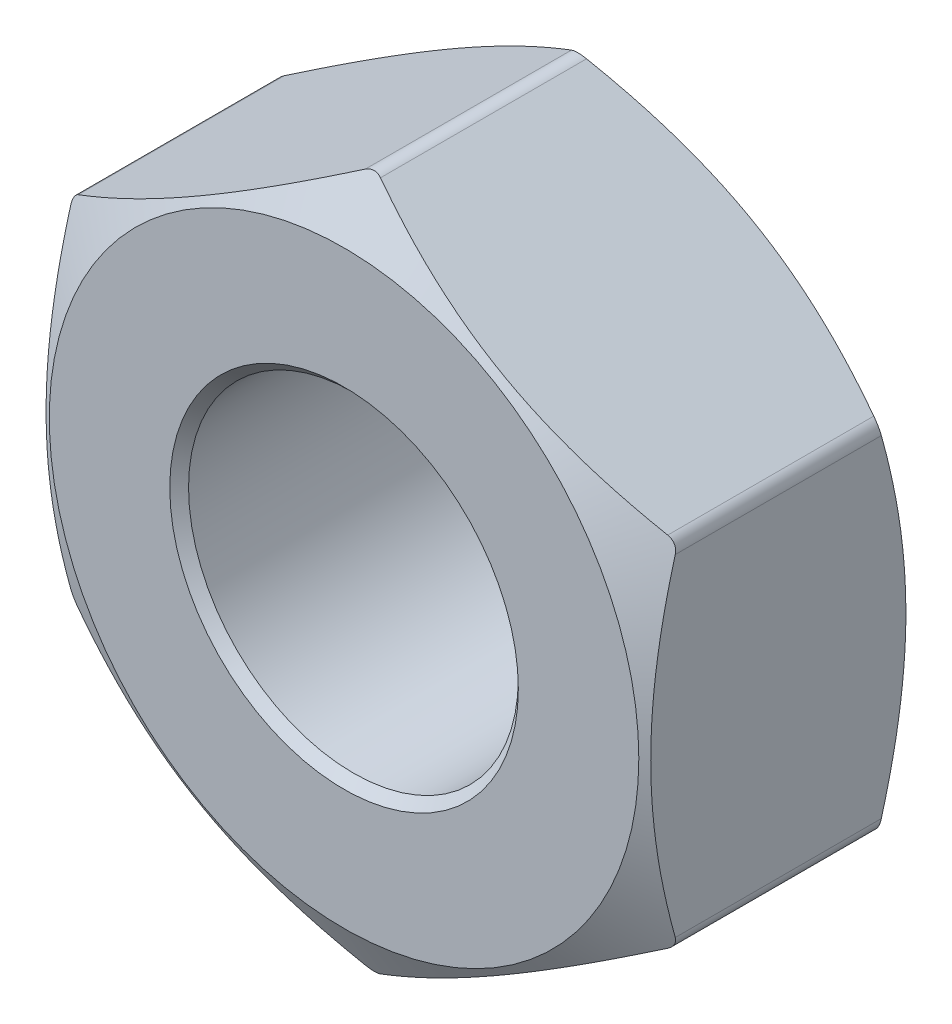
SolidWorks part; units mm, degrees
ref_plane "Front Plane" through (0, 0, 0) normal (0, 0, 1) x (1, 0, 0)
ref_plane "Top Plane" through (0, 0, 0) normal (0, 1, 0) x (1, 0, 0)
ref_plane "Right Plane" through (0, 0, 0) normal (1, 0, 0) x (0, 0, -1)
sketch "Sketch1" plane through (0, 0, 0) normal (1, 0, 0) x (0, 0, -1)
  line L0 (-1.2, 0) -> (1.2, 0) construction
  line L1 (-1.2, -2.75) -> (-1.2, 2.75) construction
  line L2 (1.2, -2.75) -> (1.2, 2.75) construction
  line L3 (-1.2, -1.5) -> (-1.2, 1.5) construction
  line L4 (-1.6688, 1.5541) -> (-1.4188, 1.1211) construction
  line L5 (-1.4188, 1.1211) -> (-1.1688, 1.5541) construction
  line L6 (-1.1688, 1.5541) -> (-1.6688, 1.5541) construction
  line L7 (-1.6531, 1.5271) -> (-1.1844, 1.5271) construction
  line L8 (-1.6375, 1.5) -> (-1.2, 1.5) construction
  line L9 (-1.45, 1.1752) -> (-1.3875, 1.1752) construction
  line L10 (-1.4188, 1.1752) -> (-1.4188, 1.1211) construction
  line L11 (-1.4188, 1.5541) -> (-1.4188, 1.5) construction
  line L12 (-1.2, 1.5854) -> (-1.1146, 1.5) construction
  point P4 (0, 0)
  point P7 (-1.2, 0)
  point P11 (1.2, 0)
  point P14 (-1.2, 0)
  point P26 (-1.4188, 1.5271)
  point P27 (-1.2, -1.5)
  dimension "Height" = 2.4
  dimension "Width" = 5.5
  dimension "Thread Size" = 3
  dimension "D1" = 60
  dimension "Thread Pitch" = 0.5
  dimension "D2" = 0.0625
  dimension "D3" = 45
sketch "Sketch2" plane through (0, 0, 0) normal (0, 0, 1) x (1, 0, 0)
  line L1 (0, 3.1754) -> (-2.75, 1.5877)
  line L2 (-2.75, 1.5877) -> (-2.75, -1.5877)
  line L3 (-2.75, -1.5877) -> (0, -3.1754)
  line L4 (0, -3.1754) -> (2.75, -1.5877)
  line L5 (2.75, -1.5877) -> (2.75, 1.5877)
  line L6 (2.75, 1.5877) -> (0, 3.1754)
  circle A0 centre (0, 0) radius 2.75 construction
  circle A1 centre (0, 0) radius 1.5
extrude "Boss-Extrude1" add sketch "Sketch2" along normal up to vertex (1.2 mm away) and the other way up to vertex (1.2 mm away) up to point (0, -2.75, 1.2) other way up to point (0, -2.75, -1.2)
sketch "Sketch3" plane through (0, 0, 1.2) normal (0, 0, 1) x (1, 0, 0)
  circle A0 centre (0, 0) radius 2.6812
  dimension "D1" = 5.3625
extrude "Cut-Extrude1" cut sketch "Sketch3" against normal through all draft 60 flip side to cut
fillet "Fillet1" radius 0.1375 6 edges at (2.75, -1.5877, -0.1427) (0, -3.1754, -0.1427) (-2.75, -1.5877, -0.1427) (-2.75, 1.5877, -0.1427) (2.75, 1.5877, -0.1427) (0, 3.1754, -0.1427)
sketch "Sketch8" plane through (0, 0, 1.2) normal (0, 0, 1) x (1, 0, 0)
  circle A0 centre (0, 0) radius 1.5854
extrude "Cut-Extrude4" cut sketch "Sketch8" against normal through all draft 45
mirror "Mirror1" about plane through (0, 0, 0) normal (0, 0, 1) of "Cut-Extrude4", "Cut-Extrude1"
sketch "Sketch4" [suppressed] plane through (0, 0, 0) normal (1, 0, 0) x (0, 0, -1)
  line L1 (-1.6531, 1.5271) -> (-1.45, 1.1752)
  line L2 (-1.45, 1.1752) -> (-1.3875, 1.1752)
  line L3 (-1.3875, 1.1752) -> (-1.1844, 1.5271)
  line L4 (-1.6531, 1.5271) -> (-1.1844, 1.5271) construction
  line L5 (-1.6531, 1.5271) -> (-1.1844, 1.5271)
sketch "Sketch5" [suppressed] plane through (0, 0, 1.2) normal (0, 0, 1) x (1, 0, 0)
  circle A0 centre (0, 0) radius 1.5 construction
  circle A1 centre (0, 0) radius 1.5
curve "Helix/Spiral1" [suppressed] pitch 0.5 height 2.9 turns 5.8
sweep "Sweep1" [suppressed] add profiles "Sketch4" path "Helix/Spiral1"
sketch "Sketch6" [suppressed] plane through (0, 0, 1.2) normal (0, 0, 1) x (1, 0, 0)
  circle A0 centre (0, 0) radius 1.5854 construction
  circle A1 centre (0, 0) radius 1.5854
extrude "Cut-Extrude2" [suppressed] cut sketch "Sketch6" along normal through all and the other way through all draft 45
sketch "Sketch7" [suppressed] plane through (0, 0, -1.2) normal (0, 0, -1) x (-1, 0, 0)
  circle A1 centre (0, 0) radius 1.5854
  circle A2 centre (0, 0) radius 1.5854
  dimension "D1" = 0
extrude "Cut-Extrude3" [suppressed] cut sketch "Sketch7" along normal through all and the other way through all draft 45
equation "\"D2@Sketch1\"=\"Thread Pitch@Sketch1\"/8"
equation "\"D4@Helix/Spiral1\"=\"Thread Pitch@Sketch1\""
equation "\"D3@Helix/Spiral1\"=\"Height@Sketch1\"+\"Thread Pitch@Sketch1\""
equation "\"D1@Sketch3\"=\"Width@Sketch1\"*.975"
equation "\"D1@Fillet1\"=\"Width@Sketch1\"*.025"
